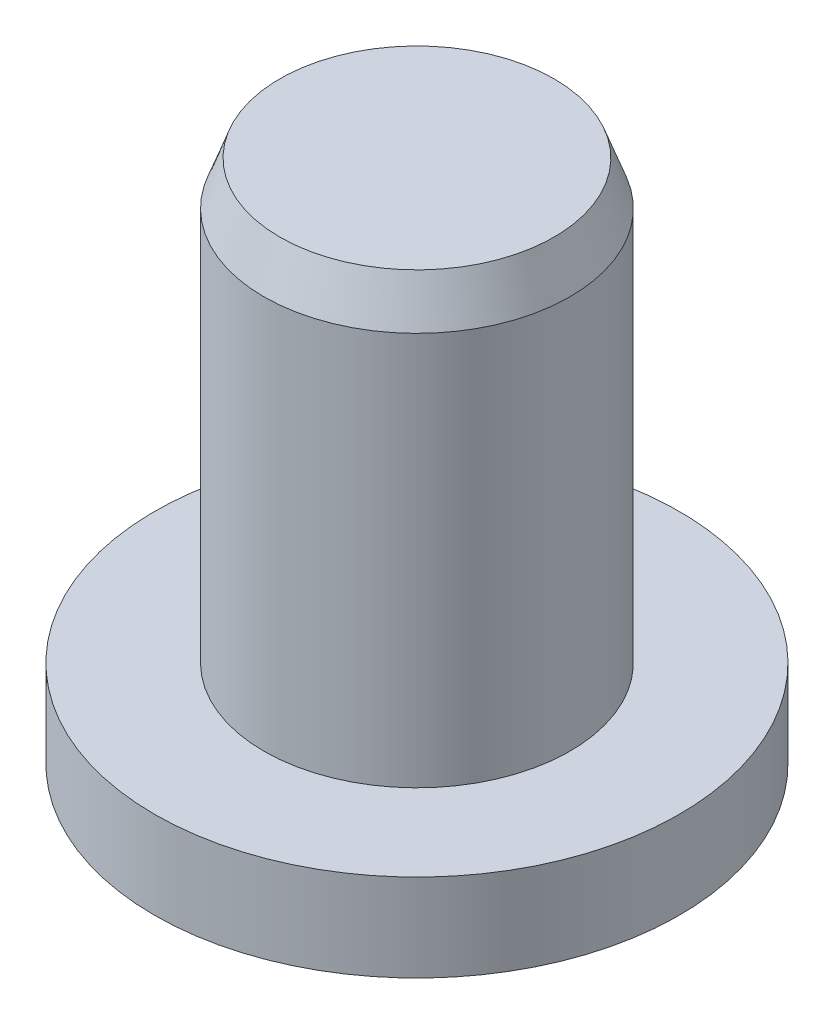
SolidWorks part; units mm, degrees
ref_plane "Front Plane" through (0, 0, 0) normal (0, 0, 1) x (1, 0, 0)
ref_plane "Top Plane" through (0, 0, 0) normal (0, 1, 0) x (1, 0, 0)
ref_plane "Right Plane" through (0, 0, 0) normal (1, 0, 0) x (0, 0, -1)
sketch "Sketch1" plane through (0, 0, 0) normal (0, 1, 0) x (1, 0, 0)
  circle A0 centre (0, 0) radius 6
  dimension "D1" = 12
extrude "Boss-Extrude1" add sketch "Sketch1" along normal blind 2
sketch "Sketch2" plane through (0, 2, 0) normal (0, 1, 0) x (1, 0, 0)
  circle A0 centre (0, 0) radius 3.5
  dimension "D1" = 7
extrude "Boss-Extrude2" add sketch "Sketch2" along normal blind 10
chamfer "Chamfer1" distance 1 angle 20 1 edges at (0, 12, 3.5) first distance on face at (0, 12, 3.5)
